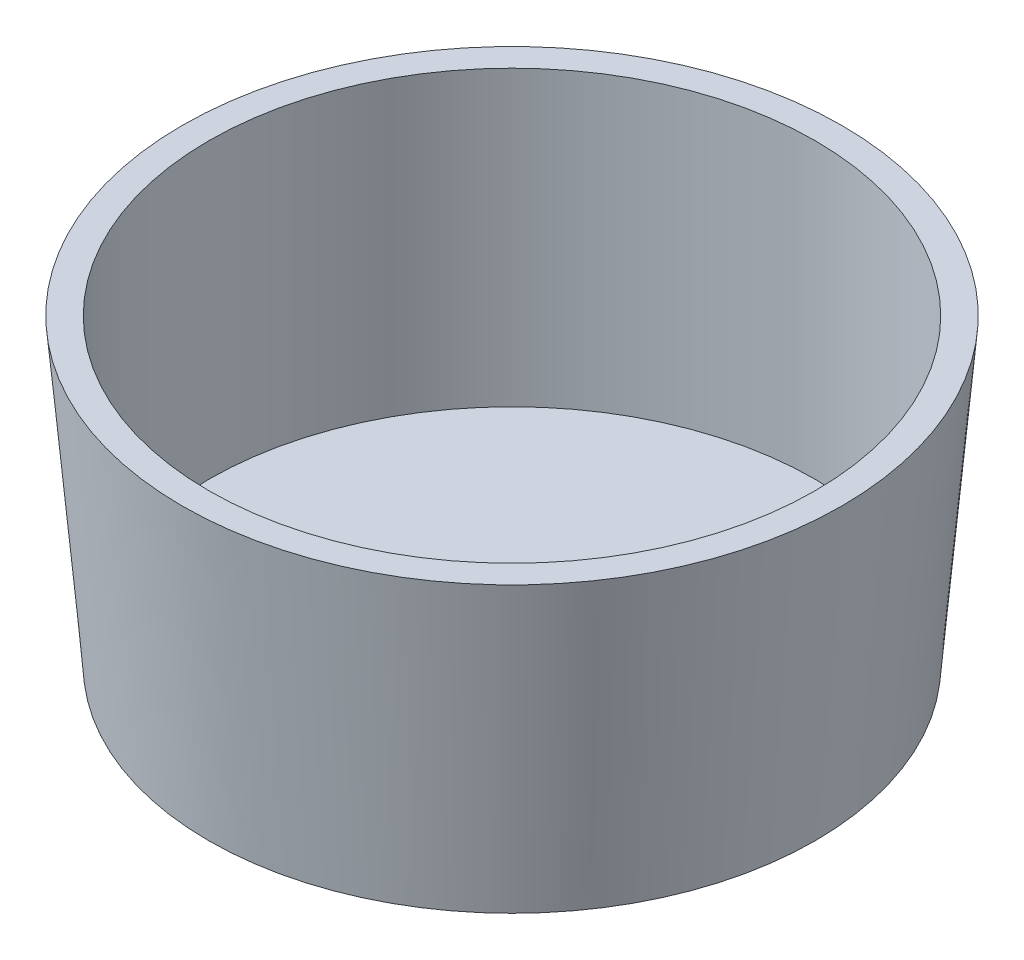
SolidWorks part; units mm, degrees
ref_plane "Front Plane" through (0, 0, 0) normal (0, 0, 1) x (1, 0, 0)
ref_plane "Top Plane" through (0, 0, 0) normal (0, 1, 0) x (1, 0, 0)
ref_plane "Right Plane" through (0, 0, 0) normal (1, 0, 0) x (0, 0, -1)
sketch "Sketch1" plane through (0, 0, 0) normal (0, 1, 0) x (1, 0, 0)
  circle A0 centre (0, 0) radius 152.4
  dimension "D1" = 304.8
extrude "Boss-Extrude1" add sketch "Sketch1" along normal blind 152.4 draft 5 draft outward yes
extrude "Cut-Extrude2" cut sketch "Sketch1<3>" along normal through all from offset 5
sketch "Sketch1<3>" plane through (0, 0, 0) normal (0, 1, 0) x (1, 0, 0) same geometry as "Sketch1"
sketch "Sketch3" plane through (0, 0, 0) normal (0, 1, 0) x (1, 0, 0)
  line L0 (0, 187.3827) -> (0, -187.3827) construction
  line L1 (0, 0) -> (215.4978, 0) construction
  arc A0 (215.4978, 0) -> (159.4065, 45.3552) centre (165.6788, -4.2498) ccw
  circle A1 centre (0, 0) radius 165.7333 construction
  arc A2 (215.4978, 0) -> (159.4065, -45.3552) centre (165.6788, 4.2498) cw
  arc A3 (-215.4978, 0) -> (-159.4065, -45.3552) centre (-165.6788, 4.2498) ccw
  arc A4 (-215.4978, 0) -> (-159.4065, 45.3552) centre (-165.6788, -4.2498) cw
  point P9 (0, 0)
  point P12 (194.3506, 23.2243)
  point P13 (183.7758, 23.6006)
  point P14 (193.5364, 22.6954)
  point P15 (163.0382, -29.7668)
  point P16 (210.2289, 0)
  point P17 (215.4978, 0)
  dimension "D1" = 50
sketch "Sketch4" plane through (0, 0, 0) normal (1, 0, 0) x (0, 0, -1)
  line L0 (0, 258.6017) -> (0, -7.8711) construction
  line L1 (0, 125.3653) -> (89.9113, 125.3653) construction
  circle A0 centre (60.7885, 125.3653) radius 9.525
  dimension "D1" = 19.05
